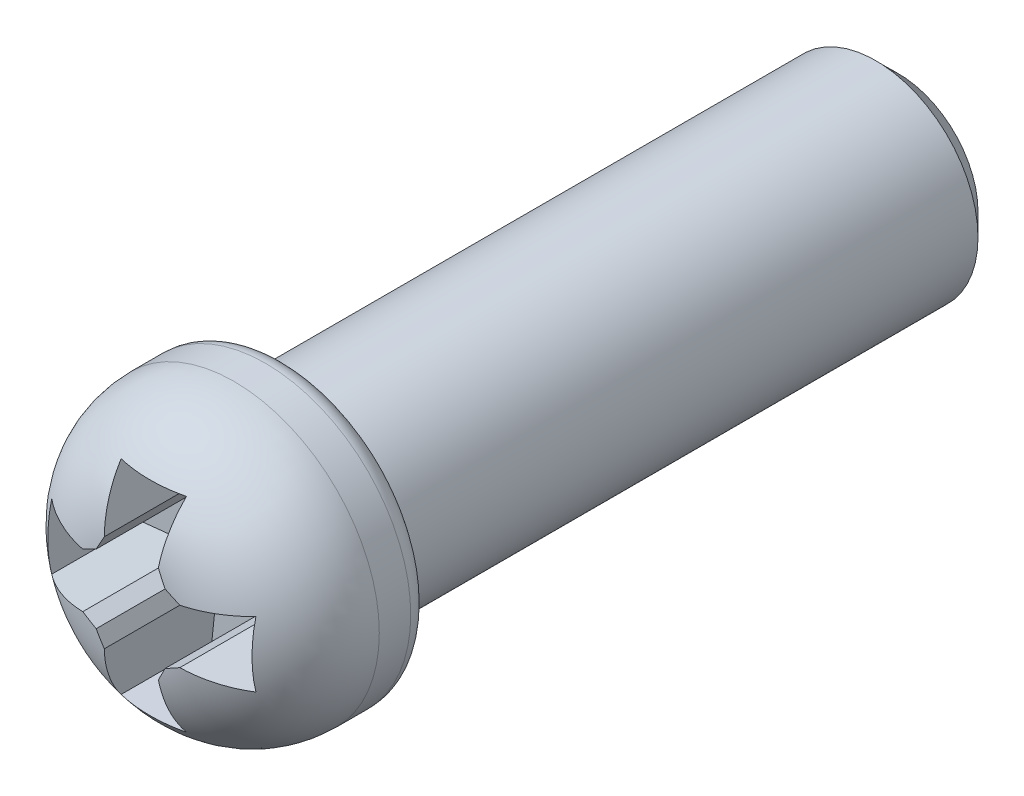
SolidWorks part; units mm, degrees
ref_plane "Front Plane" through (0, 0, 0) normal (0, 0, 1) x (1, 0, 0)
ref_plane "Top Plane" through (0, 0, 0) normal (0, 1, 0) x (1, 0, 0)
ref_plane "Right Plane" through (0, 0, 0) normal (1, 0, 0) x (0, 0, -1)
ref_plane "Plane1" through (0, 0, 0) normal (1, 0, 0) x (0, 0, -1)
sketch "Sketch1" plane through (0, 0, 0) normal (1, 0, 0) x (0, 0, -1)
  line L0 (-1.905, 0) -> (-1.905, 0.508)
  line L1 (-0.635, 1.778) -> (-0.25, 1.778)
  line L2 (0, 1.528) -> (0, 1.25)
  line L3 (0, 1.25) -> (7.224, 1.25)
  line L4 (7.224, 1.25) -> (7.5, 0.974)
  line L5 (7.5, 0.974) -> (7.5, 0)
  line L6 (7.5, 0) -> (-1.905, 0)
  line L7 (7.5, 0) -> (-1.905, 0) construction
  arc A0 (-1.905, 0.508) -> (-0.635, 1.778) centre (-0.635, 0.508) cw
  arc A1 (-0.25, 1.778) -> (0, 1.528) centre (-0.25, 1.528) cw
revolve "Revolve1" add sketch "Sketch1" angle 360 about L7 reverse direction yes
cosmetic thread "Cosmetic Thread1" parameters "D1"=7.5, "D2"=1.948
ref_plane "Plane2" through (0, 0, 0.508) normal (0, 0, 1) x (1, 0, 0)
sketch "Sketch2" plane through (0, 0, 0.508) normal (0, 0, 1) x (1, 0, 0)
  line L0 (-1.25, 0.4) -> (-1.25, -0.4)
  line L1 (-1.25, -0.4) -> (-0.5941, -0.3311)
  line L2 (-0.5941, -0.3311) -> (-0.422, -0.422)
  line L3 (-0.422, -0.422) -> (-0.3311, -0.5941)
  line L4 (-0.3311, -0.5941) -> (-0.4, -1.25)
  line L5 (-0.4, -1.25) -> (0.4, -1.25)
  line L6 (0.4, -1.25) -> (0.3311, -0.5941)
  line L7 (0.3311, -0.5941) -> (0.422, -0.422)
  line L8 (0.422, -0.422) -> (0.5941, -0.3311)
  line L9 (0.5941, -0.3311) -> (1.25, -0.4)
  line L10 (1.25, -0.4) -> (1.25, 0.4)
  line L11 (1.25, 0.4) -> (0.5941, 0.3311)
  line L12 (0.5941, 0.3311) -> (0.422, 0.422)
  line L13 (0.422, 0.422) -> (0.3311, 0.5941)
  line L14 (0.3311, 0.5941) -> (0.4, 1.25)
  line L15 (0.4, 1.25) -> (-0.4, 1.25)
  line L16 (-0.4, 1.25) -> (-0.3311, 0.5941)
  line L17 (-0.3311, 0.5941) -> (-0.422, 0.422)
  line L18 (-0.422, 0.422) -> (-0.5941, 0.3311)
  line L19 (-0.5941, 0.3311) -> (-1.25, 0.4)
extrude "Cut-Extrude1" cut sketch "Sketch2" along normal blind 1.524
